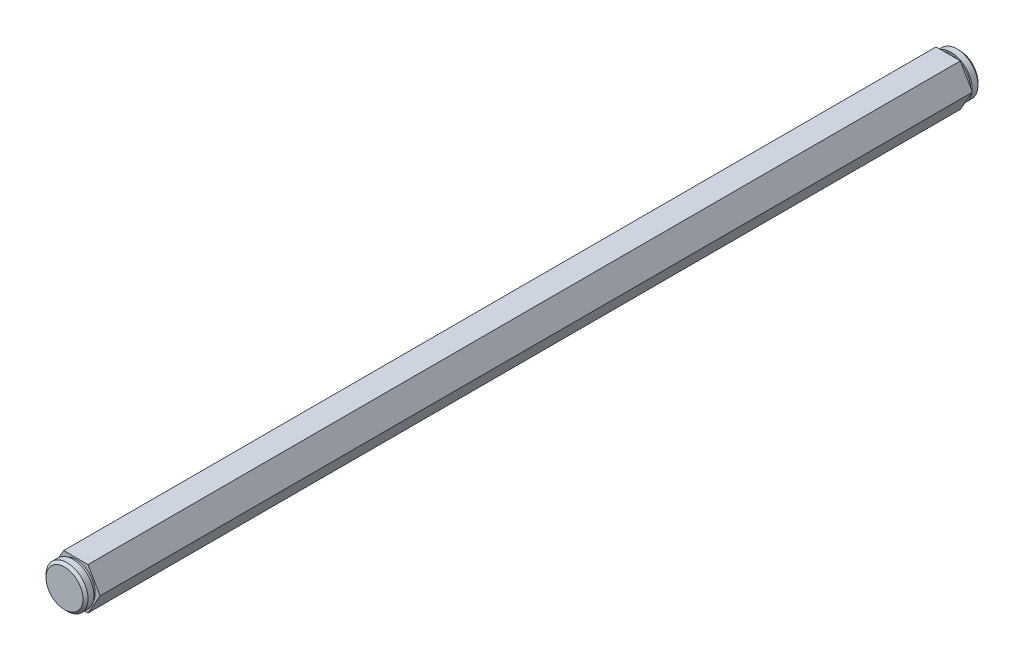
SolidWorks part; units mm, degrees
ref_plane "Front Plane" through (0, 0, 0) normal (0, 0, 1) x (1, 0, 0)
ref_plane "Top Plane" through (0, 0, 0) normal (0, 1, 0) x (1, 0, 0)
ref_plane "Right Plane" through (0, 0, 0) normal (1, 0, 0) x (0, 0, -1)
sketch "Sketch1" plane through (0, 0, 0) normal (0, 0, 1) x (1, 0, 0)
  line L1 (7.3323, 0) -> (3.6662, 6.35)
  line L2 (3.6662, 6.35) -> (-3.6662, 6.35)
  line L3 (-3.6662, 6.35) -> (-7.3323, 0)
  line L4 (-7.3323, 0) -> (-3.6662, -6.35)
  line L5 (-3.6662, -6.35) -> (3.6662, -6.35)
  line L6 (3.6662, -6.35) -> (7.3323, 0)
  circle A0 centre (0, 0) radius 6.35 construction
  dimension "D1" = 12.7
extrude "Boss-Extrude1" add sketch "Sketch1" along normal mid plane 263.525
sketch "Sketch2" plane through (0, 0, 131.7625) normal (0, 0, 1) x (1, 0, 0)
  circle A0 centre (0, 0) radius 5.8547
  dimension "D1" = 11.7094
extrude "Boss-Extrude2" add sketch "Sketch2" along normal blind 0.889
sketch "Sketch3" plane through (0, 0, 132.6515) normal (0, 0, 1) x (1, 0, 0)
  circle A0 centre (0, 0) radius 6.35
  dimension "D1" = 12.7
extrude "Boss-Extrude3" add sketch "Sketch3" along normal blind 2.54
chamfer "Chamfer1" distance 0.762 angle 45 1 edges at (6.35, 0, 135.1915)
mirror "Mirror1" about plane through (0, 0, 0) normal (0, 0, 1) of "Chamfer1", "Boss-Extrude2", "Boss-Extrude3"
